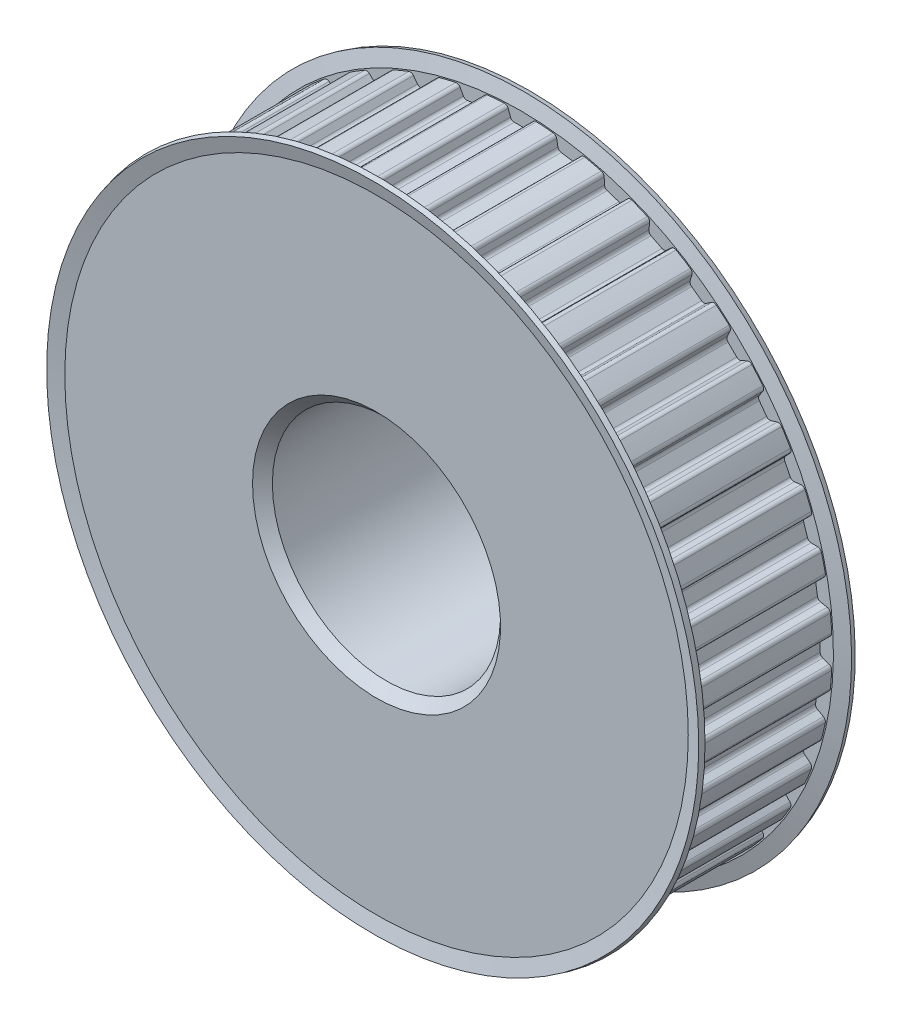
SolidWorks part; units mm, degrees
material "Д16Т ГОСТ 4784-74"
ref_plane "Front" through (0, 0, 0) normal (0, 0, 1) x (1, 0, 0)
ref_plane "Top" through (0, 0, 0) normal (0, 1, 0) x (1, 0, 0)
ref_plane "Right" through (0, 0, 0) normal (1, 0, 0) x (0, 0, -1)
sketch "support-front-body" plane through (0, 0, 0) normal (0, 0, 1) x (1, 0, 0)
  line L0 (0, 0) -> (0, 31.425) construction
  line L1 (0, 0) -> (0, -31.425) construction
  line L2 (0, 0) -> (31.425, 0) construction
  line L3 (0, 0) -> (-31.425, 0) construction
  circle A0 centre (0, 0) radius 31.425
  dimension "diam-outer" = 62.85
sketch "support-right-body" plane through (0, 0, 0) normal (1, 0, 0) x (0, 0, -1)
  line L0 (0, 0) -> (15, 0) construction
  line L1 (0, 31.425) -> (15, 31.425)
  line L2 (0, 31.425) -> (0, -31.425)
  line L3 (0, -31.425) -> (15, -31.425)
  line L4 (15, 31.425) -> (15, -31.425)
  dimension "width" = 15
sketch "support-right-hub" plane through (0, 0, 0) normal (1, 0, 0) x (0, 0, -1)
  line L0 (21, 0) -> (15, 0) construction
  line L1 (15, 20) -> (21, 20)
  line L2 (15, 20) -> (15, -20)
  line L3 (15, -20) -> (21, -20)
  line L4 (21, 20) -> (21, -20)
  line L5 (15, 31.425) -> (15, -31.425) construction
  line L6 (0, 0) -> (15, 0) construction
  line L8 (0, 31.425) -> (0, -31.425) construction
  dimension "diam-hub" = 40
  dimension "dist-hub" = 21
sketch "support-right-bore" plane through (0, 0, 0) normal (1, 0, 0) x (0, 0, -1)
  line L0 (0, 31.425) -> (0, -31.425) construction
  line L1 (0, 4) -> (21, 4)
  line L2 (0, 4) -> (0, -4)
  line L3 (0, -4) -> (21, -4)
  line L4 (21, 20) -> (21, -20) construction
  line L5 (21, 0) -> (0, 0) construction
  line L6 (0, 0) -> (15, 0) construction
  line L7 (21, 4) -> (21, -4)
  line L8 (21, -4) -> (21, 4) construction
  dimension "diam-bore" = 8
sketch "support-stop-screw-hole" plane through (0, 0, 0) normal (1, 0, 0) x (0, 0, -1)
  line L1 (6.5667, 11) -> (9.4333, 11)
  line L2 (6.5667, 11) -> (6.5667, -1)
  line L3 (8, -1) -> (9.4333, -1)
  line L4 (9.4333, 11) -> (9.4333, -1)
  line L5 (8, -1) -> (8, 11) construction
  line L6 (8, -1) -> (6.5667, -1)
  line L7 (0, 0) -> (8, 0) construction
  line L8 (0, 31.425) -> (0, -31.425) construction
  dimension "diam-stop-screw-hole" = 2.8665
  dimension "dist-stop-screw-hole" = 8
  dimension "depth-stop-screw-hole" = 12
  dimension "angle-stop-screw-hole" = 180
  dimension "height-stop-screw-hole" = 11
sketch "support-front-keygroove" plane through (0, 0, 0) normal (0, 0, 1) x (1, 0, 0)
  line L0 (0, 0) -> (0, -4) construction
  line L1 (-1, 4) -> (1, 4)
  line L2 (-1, 4) -> (-1, 1.8)
  line L3 (-1, 1.8) -> (1, 1.8)
  line L4 (1, 4) -> (1, 1.8)
  line L5 (0, 0) -> (0, 4) construction
  circle A0 centre (0, 0) radius 4 construction
  dimension "width-keygroove" = 2
  dimension "dist-keygroove" = 8
  dimension "height-keygroove" = 2.2
sketch "support-front-tooth" plane through (0, 0, 0) normal (0, 0, 1) x (1, 0, 0)
  line L0 (0, 0) -> (0, 32.5831) construction
  line L1 (-1.2259, 31.1204) -> (-0.9958, 30.4882)
  line L2 (-1.6224, 32.5831) -> (1.6224, 32.5831)
  line L3 (1.6224, 32.5831) -> (1.6224, 31.3831)
  line L4 (-1.6224, 32.5831) -> (-1.6224, 31.3831)
  line L5 (-2.5, 32.5831) -> (2.5, 32.5831) construction
  line L6 (1.6224, 31.3831) -> (2.5, 32.5831) construction
  line L7 (0, 31.425) -> (0, 30.225) construction
  line L8 (0, 31.425) -> (1.6224, 31.425) construction
  line L10 (-0.6199, 30.225) -> (0.6199, 30.225)
  line L11 (1.2259, 31.1204) -> (0.9958, 30.4882)
  line L12 (-0.9958, 30.4882) -> (-0.9, 30.225) construction
  line L13 (-0.9, 30.225) -> (-0.6199, 30.225) construction
  line L14 (0.9958, 30.4882) -> (0.9, 30.225) construction
  line L15 (0.9, 30.225) -> (0.6199, 30.225) construction
  circle A0 centre (0, 0) radius 31.425 construction
  arc A1 (-0.9958, 30.4882) -> (-0.6199, 30.225) centre (-0.6199, 30.625) ccw
  arc A3 (1.6224, 31.3831) -> (1.2259, 31.1204) centre (1.6018, 30.9836) ccw
  circle A4 centre (0, 0) radius 31.425 construction
  arc A5 (-1.6224, 31.3831) -> (-1.2259, 31.1204) centre (-1.6018, 30.9836) cw
  arc A6 (0.9958, 30.4882) -> (0.6199, 30.225) centre (0.6199, 30.625) cw
  point P26 (0, 30.225)
  dimension "rad-top" = 0.4
  dimension "rad-bottom" = 0.4
  dimension "height-tooth" = 1.2
  dimension "pitch" = 5
  dimension "angle" = 40
  dimension "width-tooth-bottom" = 1.8
sketch "support-right-flange" plane through (0, 0, 0) normal (1, 0, 0) x (0, 0, -1)
  line L0 (0, 28.7137) -> (0, 31.425)
  line L1 (15, 31.425) -> (15, -31.425) construction
  line L2 (0, 31.425) -> (0.5, 31.425) construction
  line L3 (0.5, 31.559) -> (0.1139, 33)
  line L4 (-0.3861, 32.866) -> (0.1139, 33)
  line L5 (0.5, 31.559) -> (0.5, 28.7137)
  line L6 (0.5, 28.7137) -> (0, 28.7137)
  line L7 (7.5, 31.425) -> (7.5, 0) construction
  line L8 (0, 31.425) -> (15, 31.425) construction
  line L9 (0, 31.425) -> (-0.3861, 32.866)
  line L10 (14.5, 28.7137) -> (15, 28.7138)
  line L11 (14.5, 31.559) -> (14.5, 28.7137)
  line L12 (15.3861, 32.866) -> (14.8861, 33)
  line L13 (14.5, 31.559) -> (14.8861, 33)
  line L14 (15, 31.425) -> (15.3861, 32.866)
  line L15 (15, 28.7138) -> (15, 31.425)
  line L16 (15, 0) -> (0, 0) construction
  line L17 (15, -28.7138) -> (15, -31.425)
  line L18 (15, -31.425) -> (15.3861, -32.866)
  line L19 (14.5, -31.559) -> (14.8861, -33)
  line L20 (15.3861, -32.866) -> (14.8861, -33)
  line L21 (14.5, -31.559) -> (14.5, -28.7138)
  line L22 (14.5, -28.7138) -> (15, -28.7138)
  line L23 (0.5, -28.7138) -> (0, -28.7138)
  line L24 (0.5, -31.559) -> (0.5, -28.7138)
  line L25 (-0.3861, -32.866) -> (0.1139, -33)
  line L26 (0.5, -31.559) -> (0.1139, -33)
  line L27 (0, -31.425) -> (-0.3861, -32.866)
  line L28 (0, -28.7138) -> (0, -31.425)
  line L29 (0, 0) -> (15, 0) construction
  line L30 (0, 31.425) -> (0.5, 31.559) construction
  line L31 (0.25, 28.7137) -> (0.25, 30.0694) construction
  line L32 (0.25, 30.0694) -> (0.25, 31.425) construction
  line L33 (-0.1361, 32.933) -> (0.25, 31.492) construction
  line L34 (0, 31.425) -> (15, 31.425) construction
  line L35 (0, 31.425) -> (0, -31.425) construction
  dimension "angle-flange" = 15
  dimension "thickness-flange" = 0.5
  dimension "diam-flange-inner" = 57.4275
  dimension "diam-flange-outer" = 66
  dimension "diam-flange-angle" = 62.85
ref_axis "ref-axis-center" through (0, 0, 0) along (0, 0, -1)
ref_plane "ref-plane-front" through (0, 0, 0) normal (0, 0, 1) x (1, 0, 0)
ref_plane "ref-plane-back" through (0, 0, -15) normal (0, 0, 1) x (1, 0, 0)
ref_plane "ref-plane-hub-front" through (0, 0, -15) normal (0, 0, 1) x (1, 0, 0)
ref_plane "ref-plane-hub-back" through (0, 0, -21) normal (0, 0, 1) x (1, 0, 0)
ref_plane "ref-plane-bore-front" through (0, 0, 0) normal (0, 0, 1) x (1, 0, 0)
ref_plane "ref-plane-bore-back" through (0, 0, -21) normal (0, 0, 1) x (1, 0, 0)
ref_plane "ref-plane-stop-screw-hole-top" through (0, 11, 0) normal (0, 1, 0) x (-1, 0, 0)
ref_axis "ref-axis-stop-screw-hole" through (0, -1, -8) along (0, 1, 0)
sketch "Sketch5" plane through (0, 0, 0) normal (1, 0, 0) x (0, 0, -1)
  line L0 (15, 31.425) -> (15, -31.425) construction
  line L1 (0, 31.425) -> (15, 31.425) construction
  line L2 (0, 31.425) -> (0, -31.425) construction
  line L3 (0, 0) -> (15, 0) construction
  line L4 (15, 31.425) -> (15, 0)
  line L5 (0, 31.425) -> (15, 31.425)
  line L6 (0, 31.425) -> (0, 0)
  line L7 (0, 0) -> (15, 0) construction
  line L8 (0, 0) -> (15, 0)
revolve "body" add sketch "Sketch5" angle 360 about L7
sketch "Sketch16" plane through (0, 0, 0) normal (1, 0, 0) x (0, 0, -1)
  line L0 (21, 20) -> (21, -20) construction
  line L1 (15, 20) -> (21, 20) construction
  line L2 (21, 0) -> (15, 0) construction
  line L3 (15, 20) -> (15, -20) construction
  line L4 (21, 20) -> (21, 0)
  line L5 (15, 20) -> (21, 20)
  line L6 (21, 0) -> (15, 0) construction
  line L7 (15, 20) -> (15, 0)
  line L8 (21, 0) -> (15, 0)
revolve "body-hub" add sketch "Sketch16" angle 360 about L6
sketch "Sketch17" plane through (0, 0, 0) normal (1, 0, 0) x (0, 0, -1)
  line L1 (21, 0) -> (0, 0) construction
  line L2 (0, 4) -> (21, 4) construction
  line L3 (0, 4) -> (0, -4) construction
  line L4 (21, 4) -> (21, -4) construction
  line L5 (21, 0) -> (0, 0) construction
  line L6 (0, 4) -> (21, 4)
  line L7 (0, 4) -> (0, 0)
  line L8 (21, 0) -> (0, 0)
  line L9 (21, 4) -> (21, 0)
revolve "body-bore" cut sketch "Sketch17" angle 360 about L5
sketch "Sketch19" plane through (0, 0, 0) normal (1, 0, 0) x (0, 0, -1)
  line L0 (6.5667, 11) -> (9.4333, 11) construction
  line L1 (8, -1) -> (8, 11) construction
  line L2 (9.4333, 11) -> (9.4333, -1) construction
  line L3 (8, -1) -> (9.4333, -1) construction
  line L4 (8, 11) -> (9.4333, 11)
  line L5 (8, -1) -> (8, 11) construction
  line L6 (9.4333, 11) -> (9.4333, -1)
  line L7 (8, -1) -> (9.4333, -1)
  line L8 (8, -1) -> (8, 11)
revolve "body-stop-screw-hole" [suppressed] cut sketch "Sketch19" angle 360 about L5
pattern_circular "pattern-stop-screw-hole" [suppressed] count 2 every 90 about axis through (0, 0, 0) along (0, 0, -1)
sketch "Sketch21" plane through (0, 0, 0) normal (0, 0, 1) x (1, 0, 0)
  line L0 (-1, 4) -> (1, 4) construction
  line L1 (-1, 4) -> (-1, 1.8) construction
  line L2 (-1, 1.8) -> (1, 1.8) construction
  line L3 (1, 4) -> (1, 1.8) construction
  line L4 (-1, 4) -> (1, 4)
  line L5 (-1, 4) -> (-1, 1.8)
  line L6 (-1, 1.8) -> (1, 1.8)
  line L7 (1, 4) -> (1, 1.8)
extrude "cut-keygroove" [suppressed] cut sketch "Sketch21" against normal up to surface (17.5 mm away)
sketch "Sketch23" plane through (0, 0, 0) normal (0, 0, 1) x (1, 0, 0)
  line L6 (1.6224, 32.5831) -> (-1.6224, 32.5831)
  line L7 (1.6224, 31.3831) -> (1.6224, 32.5831)
  line L8 (0.9958, 30.4882) -> (1.2259, 31.1204)
  line L9 (-0.6199, 30.225) -> (0.6199, 30.225)
  line L10 (-1.2259, 31.1204) -> (-0.9958, 30.4882)
  line L11 (-1.6224, 32.5831) -> (-1.6224, 31.3831)
  line L12 (1.6224, 32.5831) -> (-1.6224, 32.5831)
  line L13 (1.6224, 31.3831) -> (1.6224, 32.5831)
  line L14 (0.9958, 30.4882) -> (1.2259, 31.1204)
  line L15 (-0.6199, 30.225) -> (0.6199, 30.225)
  line L16 (-1.2259, 31.1204) -> (-0.9958, 30.4882)
  line L17 (-1.6224, 32.5831) -> (-1.6224, 31.3831)
  arc A4 (1.6224, 31.3831) -> (1.2259, 31.1204) centre (1.6018, 30.9836) ccw
  arc A5 (0.6199, 30.225) -> (0.9958, 30.4882) centre (0.6199, 30.625) ccw
  arc A6 (-0.9958, 30.4882) -> (-0.6199, 30.225) centre (-0.6199, 30.625) ccw
  arc A7 (-1.2259, 31.1204) -> (-1.6224, 31.3831) centre (-1.6018, 30.9836) ccw
  arc A8 (1.6224, 31.3831) -> (1.2259, 31.1204) centre (1.6018, 30.9836) ccw
  arc A9 (0.6199, 30.225) -> (0.9958, 30.4882) centre (0.6199, 30.625) ccw
  arc A10 (-0.9958, 30.4882) -> (-0.6199, 30.225) centre (-0.6199, 30.625) ccw
  arc A11 (-1.2259, 31.1204) -> (-1.6224, 31.3831) centre (-1.6018, 30.9836) ccw
  dimension "D1" = 0
extrude "cut-tooth" cut sketch "Sketch23" against normal up to surface (15 mm away) up to plane "ref-plane-back"
pattern_circular "pattern-tooth" count 40 over 360 about axis through (0, 0, 0) along (0, 0, -1) of "cut-tooth"
sketch "Sketch25" plane through (0, 0, 0) normal (1, 0, 0) x (0, 0, -1)
  line L0 (0, 0) -> (15, 0) construction
  line L1 (0.5, 28.7137) -> (0, 28.7137) construction
  line L2 (0.5, 31.559) -> (0.5, 28.7137) construction
  line L4 (-0.3861, 32.866) -> (0.1139, 33) construction
  line L5 (0, 31.425) -> (-0.3861, 32.866) construction
  line L6 (0, 28.7137) -> (0, 31.425) construction
  line L7 (0, 0) -> (15, 0) construction
  line L8 (0.5, 28.7137) -> (0, 28.7137)
  line L9 (0.5, 31.559) -> (0.5, 28.7137)
  line L10 (-0.3861, 32.866) -> (0.1139, 33)
  line L11 (0.5, 31.559) -> (0.1139, 33) construction
  line L12 (0, 31.425) -> (-0.3861, 32.866)
  line L13 (0, 28.7137) -> (0, 31.425)
  line L14 (0.5, 31.559) -> (0.1139, 33)
revolve "body-flange-front" add sketch "Sketch25" angle 360 about L7
sketch "Sketch26" plane through (0, 0, 0) normal (1, 0, 0) x (0, 0, -1)
  line L0 (15, 0) -> (0, 0) construction
  line L1 (14.5, 28.7137) -> (15, 28.7138) construction
  line L2 (14.5, 31.559) -> (14.5, 28.7137) construction
  line L4 (15.3861, 32.866) -> (14.8861, 33) construction
  line L5 (15, 31.425) -> (15.3861, 32.866) construction
  line L6 (15, 28.7138) -> (15, 31.425) construction
  line L7 (15, 0) -> (0, 0) construction
  line L8 (14.5, 28.7137) -> (15, 28.7138)
  line L9 (14.5, 31.559) -> (14.5, 28.7137)
  line L10 (15.3861, 32.866) -> (14.8861, 33)
  line L11 (14.5, 31.559) -> (14.8861, 33) construction
  line L12 (15, 31.425) -> (15.3861, 32.866)
  line L13 (15, 28.7138) -> (15, 31.425)
  line L14 (14.5, 31.559) -> (14.8861, 33)
revolve "body-flange-back" add sketch "Sketch26" angle 360 about L7
sketch "Эскиз1" plane through (0, 0, 0) normal (0, 0, 1) x (1, 0, 0)
  line L0 (6.5, 3.7417) -> (6.5, -3.7417)
  arc A0 (6.5, 3.7417) -> (6.5, -3.7417) centre (0, 0) ccw
  dimension "D1" = 15
  dimension "D2" = 6.5
extrude "Вырез-Вытянуть1" cut sketch "Эскиз1" against normal through all
sketch "Эскиз2" plane through (0, 0, 0) normal (0, 0, 1) x (1, 0, 0)
  circle A0 centre (0, 0) radius 11.5
  dimension "D1" = 23
extrude "Вырез-Вытянуть2" cut sketch "Эскиз2" against normal blind 30
chamfer "Фаска1" distance 1 angle 45 1 edges at (11.5, 0, 0)
equation "\"diam-flange-angle@support-right-flange\" = \"diam-outer@support-front-body\""
equation "\"diam-flange-inner@support-right-flange\"=(\"diam-outer@support-front-body\" - 2 * \"height-tooth@support-front-tooth\" )  * 0.95"
